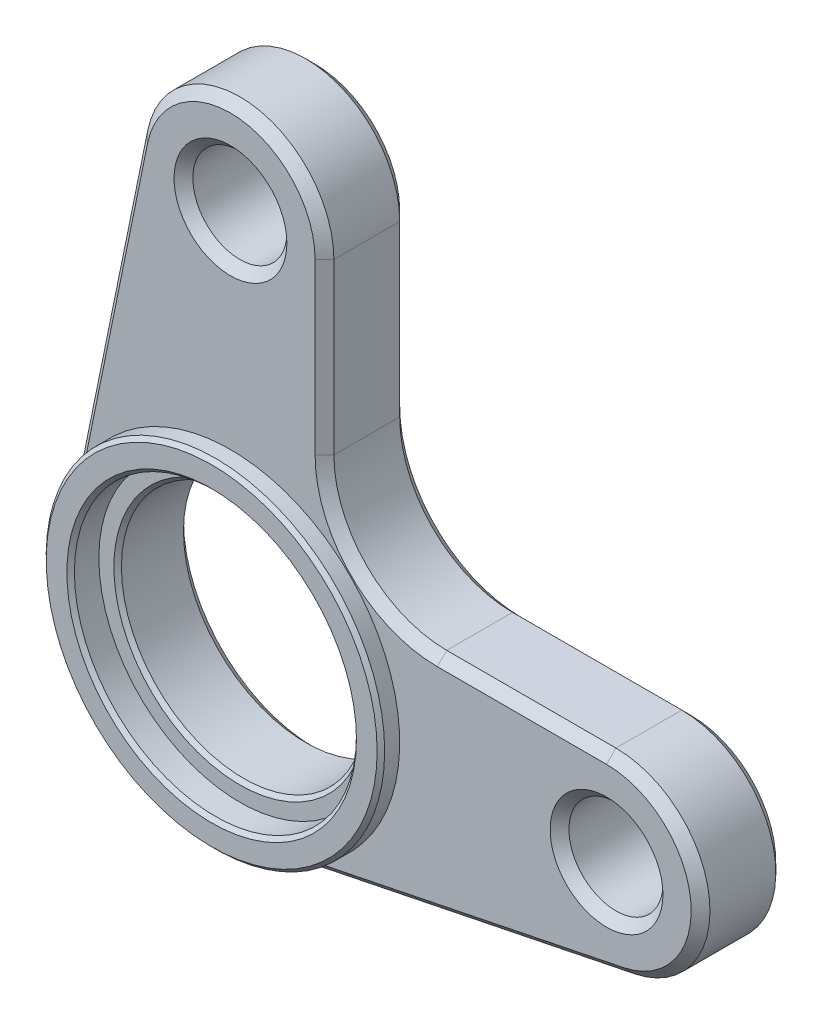
SolidWorks part; units mm, degrees
material "6061-T6 (GB)"
ref_plane "前视" through (0, 0, 0) normal (0, 0, 1) x (1, 0, 0)
ref_plane "上视" through (0, 0, 0) normal (0, 1, 0) x (1, 0, 0)
ref_plane "右视" through (0, 0, 0) normal (1, 0, 0) x (0, 0, -1)
sketch "草图1" plane through (0, 0, 0) normal (0, 0, 1) x (1, 0, 0)
  line L0 (0, 0) -> (0, 20) construction
  line L1 (0, 0) -> (20, 0) construction
  line L2 (-4.899, 21) -> (-8.8182, 1.8)
  line L3 (1.8, -8.8182) -> (21, -4.899)
  line L4 (5, 20) -> (5, 11)
  line L5 (11, 5) -> (20, 5)
  circle A0 centre (0, 0) radius 6.5
  arc A1 (-8.8182, 1.8) -> (1.8, -8.8182) centre (0, 0) ccw
  circle A2 centre (0, 20) radius 2.5
  arc A3 (5, 20) -> (-4.899, 21) centre (0, 20) ccw
  circle A4 centre (20, 0) radius 2.5
  arc A5 (21, -4.899) -> (20, 5) centre (20, 0) ccw
  arc A6 (5, 11) -> (11, 5) centre (11, 11) ccw
  dimension "D1" = 20
  dimension "D2" = 20
  dimension "D3" = 5
  dimension "D4" = 5
  dimension "D5" = 13
  dimension "D6" = 18
  dimension "D7" = 10
  dimension "D8" = 10
  dimension "D9" = 6
extrude "凸台-拉伸1" add sketch "草图1" along normal blind 4.5
sketch "草图2" plane through (0, 0, 4.5) normal (0, 0, 1) x (1, 0, 0)
  circle A0 centre (0, 0) radius 9
  arc A1 (-8.8182, 1.8) -> (1.8, -8.8182) centre (0, 0) ccw construction
  circle A2 centre (0, 0) radius 6.5 construction
  circle A3 centre (0, 0) radius 6.5
extrude "凸台-拉伸2" add sketch "草图2" along normal blind 1
sketch "草图3" plane through (0, 0, 5.5) normal (0, 0, 1) x (1, 0, 0)
  circle A0 centre (0, 0) radius 7.5
  dimension "D1" = 15
extrude "切除-拉伸1" cut sketch "草图3" against normal blind 1.5
chamfer "倒角1" distance 0.5 angle 45 20 edges at (22.5, 0, 0) (2.5, 20, 0) (6.5, 0, 0) (15.5, 5, 0) (6.7574, 6.7574, 0) (5, 15.5, 0) (0.5025, 24.9747, 0) (-6.8586, 11.4, 0) (-6.364, -6.364, 0) (11.4, -6.8586, 0) (24.9747, 0.5025, 0) (11.4, -6.8586, 4.5) (24.9747, 0.5025, 4.5) (15.5, 5, 4.5) (-6.8586, 11.4, 4.5) (6.7574, 6.7574, 4.5) (0.5025, 24.9747, 4.5) (5, 15.5, 4.5) (22.5, 0, 4.5) (2.5, 20, 4.5)
chamfer "倒角2" distance 0.2 angle 45 3 edges at (9, 0, 5.5) (7.5, 0, 5.5) (6.5, 0, 4)
